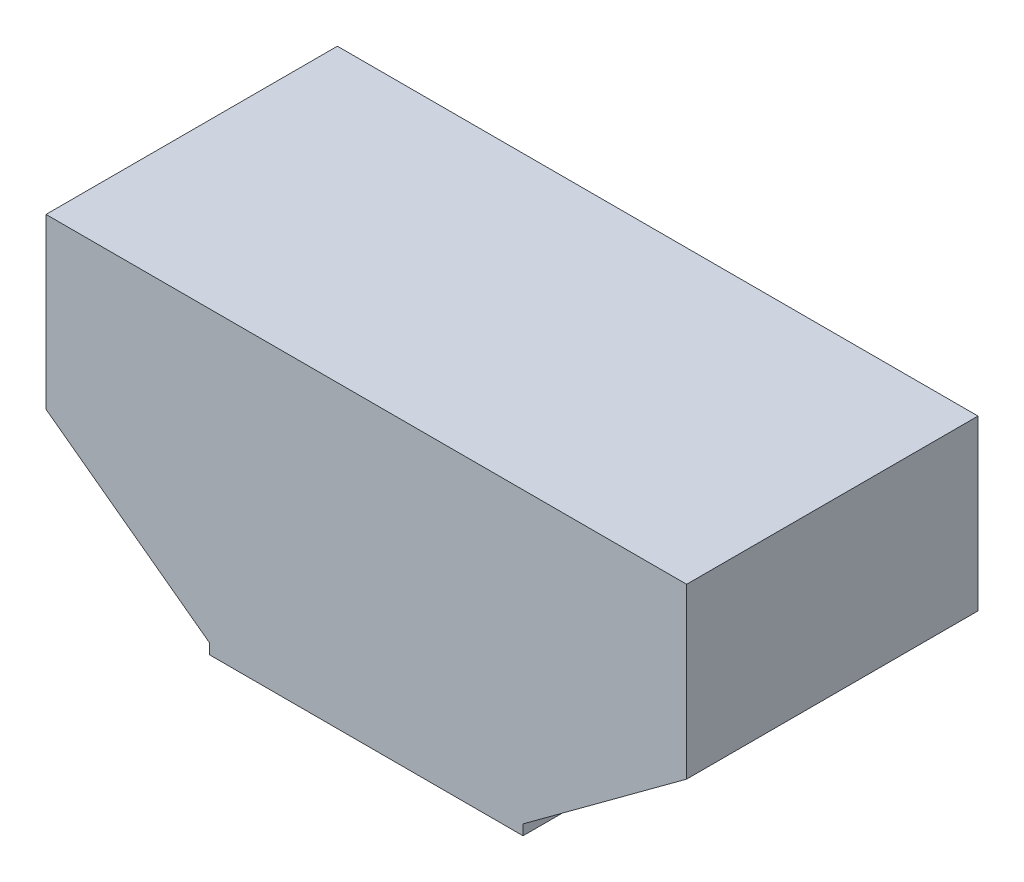
SolidWorks part; units mm, degrees
ref_plane "Front Plane" through (0, 0, 0) normal (0, 0, 1) x (1, 0, 0)
ref_plane "Top Plane" through (0, 0, 0) normal (0, 1, 0) x (1, 0, 0)
ref_plane "Right Plane" through (0, 0, 0) normal (1, 0, 0) x (0, 0, -1)
sketch "Sketch1" plane through (0, 0, 0) normal (0, 0, 1) x (1, 0, 0)
  line L0 (-2063.2072, -609.6) -> (2063.2072, -609.6) construction
  line L1 (-2087.4164, -520.7) -> (2087.4164, -520.7) construction
  line L2 (0, 0) -> (0, -520.7) construction
  line L3 (-577.85, -2072.3236) -> (577.85, -2072.3236)
  line L6 (577.85, -2072.3236) -> (577.85, -2034.2236)
  line L7 (577.85, -2034.2236) -> (-577.85, -2034.2236) construction
  line L8 (-577.85, -2034.2236) -> (-577.85, -2072.3236)
  line L9 (-577.85, -2034.2236) -> (-1181.1, -1589.7236)
  line L10 (-1181.1, -1589.7236) -> (-1181.1, -967.4236)
  line L11 (-1181.1, -967.4236) -> (1181.1, -967.4236)
  line L12 (1181.1, -967.4236) -> (1181.1, -1589.7236)
  line L13 (1181.1, -1589.7236) -> (577.85, -2034.2236)
  circle A0 centre (0, 0) radius 2240.28 construction
  circle A1 centre (0, 0) radius 2151.38 construction
  circle A4 centre (0, -520.7) radius 274.5589 construction
  point P6 (0, -2151.38)
  point P21 (0, -2034.2236)
  point P22 (239.5256, -2505.9382)
  point P23 (239.5256, -2505.9382)
  dimension "D1" = 4480.56
  dimension "D2" = 88.9
  dimension "D5" = 1155.7
  dimension "D7" = 622.3
  dimension "D3" = 1541.78
  dimension "D4" = 88.9
  dimension "D6" = 1066.8
  dimension "D8" = 38.1
  dimension "D9" = 2362.2
extrude "Boss-Extrude1" add sketch "Sketch1" along normal blind 1074.42
